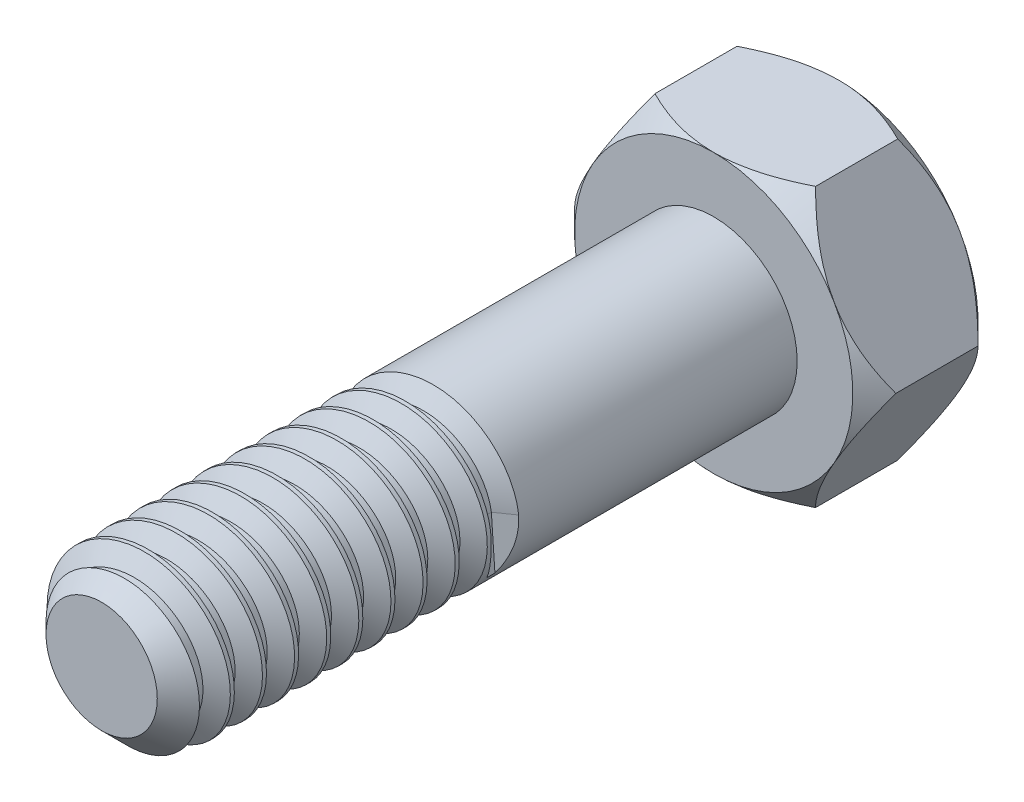
SolidWorks part; units mm, degrees
ref_plane "Front Plane" through (0, 0, 0) normal (0, 0, 1) x (1, 0, 0)
ref_plane "Top Plane" through (0, 0, 0) normal (0, 1, 0) x (1, 0, 0)
ref_plane "Right Plane" through (0, 0, 0) normal (1, 0, 0) x (0, 0, -1)
sketch "Sketch1" plane through (0, 0, 0) normal (0, 0, 1) x (1, 0, 0)
  line L1 (1.4434, -2.5) -> (2.8868, 0)
  line L2 (2.8868, 0) -> (1.4434, 2.5)
  line L3 (1.4434, 2.5) -> (-1.4434, 2.5)
  line L4 (-1.4434, 2.5) -> (-2.8868, 0)
  line L5 (-2.8868, 0) -> (-1.4434, -2.5)
  line L6 (-1.4434, -2.5) -> (1.4434, -2.5)
  circle A0 centre (0, 0) radius 2.5 construction
  dimension "D1" = 5
extrude "Boss-Extrude1" add sketch "Sketch1" along normal mid plane 2.25
sketch "Sketch2" plane through (0, 0, 1.125) normal (0, 0, 1) x (1, 0, 0)
  line L0 (-1.4434, 2.5) -> (-2.8868, 0) construction
  circle A0 centre (0, 0) radius 2.5
extrude "Cut-Extrude1" cut sketch "Sketch2" against normal through all draft 45 flip side to cut contours A0
mirror "Mirror1" about plane through (0, 0, 0) normal (0, 0, 1) of "Cut-Extrude1"
sketch "Sketch3" plane through (0, 0, 1.125) normal (0, 0, 1) x (1, 0, 0)
  circle A0 centre (0, 0) radius 1.5
  dimension "D1" = 3
extrude "Boss-Extrude2" add sketch "Sketch3" along normal blind 11
chamfer "Chamfer1" distance 0.5 angle 45 1 edges at (1.5, 0, 12.125)
thread "Thread1" pitch 0.5773 method cut profile "Thread Profile2" start angle 4, offset 5, length 0, pitch 0.5773, diameter 3
ref_plane "Plane2" through (1.4963, 0.1046, 6.125) normal (0.0698, -0.9976, 0) x (0.9976, 0.0698, 0)
sketch "Thread Profile2" plane through (1.4963, 0.1046, 6.125) normal (0.0698, -0.9976, 0) x (0.9976, 0.0698, 0)
  line L0 (0, 0) -> (0, 0.5773) construction
  line L11 (0, 0) -> (0, 0.5051)
  line L12 (0, 0.5051) -> (-0.3125, 0.3247)
  line L13 (-0.3125, 0.3247) -> (-0.3125, 0.1804)
  line L15 (-0.3125, 0.1804) -> (0, 0)
  line L17 (-0.3125, 0.2526) -> (0, 0.2526) construction
  point P2 (0, 0)
  dimension "Pitch" = 0.5773
  dimension "Profile_Angle" = 60
  dimension "Profile_Land" = 0.1443
  dimension "Profile_Height" = 0.3125
sketch "Sketch13" plane through (0, 0, 0) normal (-0.0698, 0.9976, 0) x (0.9976, 0.0698, 0)
  line L4 (1.5, -6.125) -> (1.1875, -6.3054)
  line L5 (1.1875, -6.3054) -> (1.1875, -6.4497)
  line L6 (1.1875, -6.4497) -> (1.5, -6.6301)
  line L7 (1.5, -6.6301) -> (1.5, -6.125)
  line L8 (1.5, -6.125) -> (1.1875, -6.3054)
  line L9 (1.1875, -6.3054) -> (1.1875, -6.4497)
  line L10 (1.1875, -6.4497) -> (1.5, -6.6301)
  line L11 (1.5, -6.6301) -> (1.5, -6.125)
  dimension "D1" = 0
extrude "Cut-Extrude2" cut sketch "Sketch13" against normal through all
